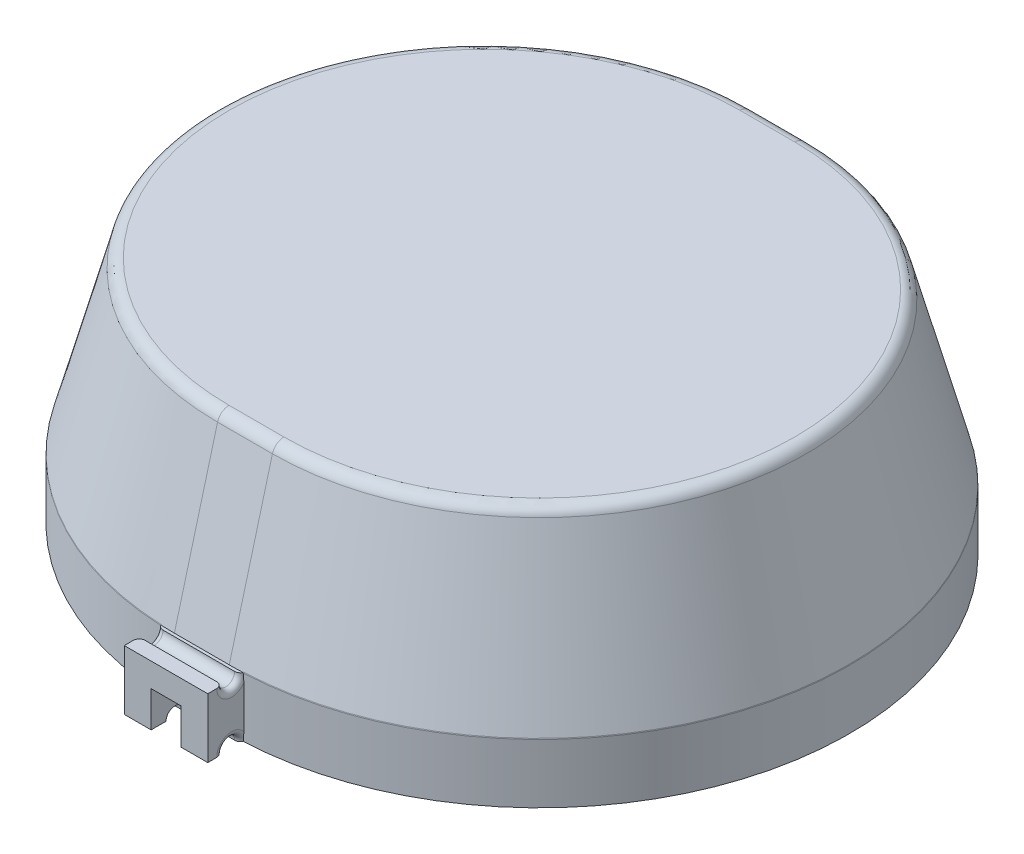
SolidWorks part; units mm, degrees
material "ABS"
ref_plane "Front Plane" through (0, 0, 0) normal (0, 0, 1) x (1, 0, 0)
ref_plane "Top Plane" through (0, 0, 0) normal (0, 1, 0) x (1, 0, 0)
ref_plane "Right Plane" through (0, 0, 0) normal (1, 0, 0) x (0, 0, -1)
ref_axis "Center" through (0, 21.7875, 0) along (0, -1, 0)
sketch "Sketch1" plane through (0, 0, 0) normal (0, 1, 0) x (1, 0, 0)
  line L0 (-2.3, 0) -> (2.3, 0) construction
  line L1 (-2.3, 25) -> (2.3, 25)
  line L2 (-2.3, -25) -> (2.3, -25)
  line L3 (-2.3, 0) -> (2.3, 0) construction
  line L4 (-2.3, 26) -> (2.3, 26)
  line L5 (-2.3, -26) -> (2.3, -26)
  arc A0 (-2.3, 25) -> (-2.3, -25) centre (-2.3, 0) ccw
  arc A1 (2.3, -25) -> (2.3, 25) centre (2.3, 0) ccw
  arc A2 (-2.3, 26) -> (-2.3, -26) centre (-2.3, 0) ccw
  arc A3 (2.3, -26) -> (2.3, 26) centre (2.3, 0) ccw
  point P2 (0, 0)
  point P9 (0, 0)
  dimension "D1" = 4.6
  dimension "D2" = 25
  dimension "D3" = 26
extrude "Boss-Extrude2" add sketch "Sketch1" along normal blind 5
sketch "Sketch2" plane through (0, 0, 0) normal (0, 1, 0) x (1, 0, 0)
  line L0 (-3.5, -25.9723) -> (-3.5, -27) construction
  line L1 (3.5, -25.9723) -> (3.5, -27) construction
  line L2 (-4.25, -25) -> (-4.25, -27)
  line L3 (4.25, -25) -> (4.25, -27)
  line L4 (-2.3, -25) -> (2.3, -25) construction
  line L5 (-4.25, -25) -> (4.25, -25)
  line L6 (0, -27) -> (0, -26) construction
  line L7 (-2.3, -26) -> (2.3, -26) construction
  line L8 (0, -27) -> (-3.5, -27) construction
  line L9 (0, -27) -> (3.5, -27) construction
  arc A0 (-3.5, -27) -> (3.5, -27) centre (0, -27) ccw construction
  arc A1 (-2.3, 26) -> (-2.3, -26) centre (-2.3, 0) ccw construction
  arc A3 (4.25, -27) -> (-4.25, -27) centre (0, -27) cw
  arc A4 (2.3, -26) -> (2.3, 26) centre (2.3, 0) ccw construction
  dimension "D1" = 2
  dimension "D2" = 0.75
  dimension "D3" = 0.75
  dimension "D4" = 3.5
ref_axis "F1" through (-2.3, 0, 0) along (0, 1, 0)
ref_axis "F2" through (2.3, 0, 0) along (0, 1, 0)
sketch "Sketch8" plane through (0, 0, 0) normal (1, 0, 0) x (0, 0, -1)
  line L1 (-25, 5) -> (-23.69, 5)
  line L2 (-25, 5) -> (-25, 3)
  line L3 (-25, 3) -> (-23.69, 3)
  line L4 (-23.69, 5) -> (-23.69, 3)
  dimension "D1" = 1.31
sweep "Sweep1" add profiles "Sketch8" path "Sketch1<2>"
sketch "Sketch1<2>" plane through (0, 0, 0) normal (0, 1, 0) x (1, 0, 0) same geometry as "Sketch1"
sketch "Sketch5" plane through (0, 0, 0) normal (-1, 0, 0) x (0, 0, 1)
  line L0 (-26, 5) -> (-22.1817, 19.25)
  line L1 (-22.1817, 19.25) -> (0, 19.25)
  line L2 (0, 19.25) -> (0, 18)
  line L3 (0, 18) -> (-21.2226, 18)
  line L4 (-21.2226, 18) -> (-24.7059, 5)
  line L7 (-24.7059, 5) -> (-26, 5)
  line L11 (-26, 5) -> (-26, 21.0394) construction
  line L12 (0, 21.7875) -> (0, -1.0375) construction
  dimension "D1" = 1.25
  dimension "D2" = 15
  dimension "D3" = 1.25
  dimension "D4" = 18
extrude "Boss-Extrude4" add sketch "Sketch5" along normal blind 2.3 and the other way blind 2.3
sketch "Sketch7" plane through (-2.3, 0, 0) normal (-1, 0, 0) x (0, 0, 1)
  line L0 (-26, 5) -> (-22.1817, 19.25)
  line L1 (-22.1817, 19.25) -> (0, 19.25)
  line L2 (0, 19.25) -> (0, 18)
  line L3 (0, 18) -> (-21.2226, 18)
  line L4 (-21.2226, 18) -> (-24.7059, 5)
  line L5 (-24.7059, 5) -> (-26, 5)
revolve "Revolve2" add sketch "Sketch7" angle 180 about axis through (-2.3, 0, 0) along (0, 1, 0)
mirror "Mirror1" about plane through (0, 0, 0) normal (0, 0, 1) of "Boss-Extrude4"
mirror "Mirror2" about plane through (0, 0, 0) normal (1, 0, 0) of "Revolve2"
sketch "Sketch11" plane through (0, 0, -25) normal (0, 0, -1) x (-1, 0, 0)
  line L0 (2.3, 5) -> (2.3, 0) construction
  line L1 (-2.3, 3) -> (2.3, 3)
  line L2 (-2.3, 3) -> (-2.3, 1.5)
  line L3 (-2.3, 1.5) -> (2.3, 1.5)
  line L4 (2.3, 3) -> (2.3, 1.5)
  line L5 (2.3, 3) -> (-2.3, 3) construction
  dimension "D1" = 1.5
extrude "Cut-Extrude5" cut sketch "Sketch11" along normal up to next (1 mm away) draft 5
fillet "Fillet8" radius 0.25 3 edges at (2.3, 2.25, -25) (0, 1.5, -25) (-2.3, 2.25, -25)
sketch "Sketch12" plane through (0, 3, 0) normal (0, -1, 0) x (1, 0, 0)
  line L0 (-3.5, 25) -> (-3.5, 29)
  line L1 (-3.5, 29) -> (3.5, 29)
  line L2 (3.5, 29) -> (3.5, 25)
  line L3 (3.5, 25) -> (-3.5, 25)
  line L4 (0, 25) -> (0, 23.69) construction
  line L5 (2.3, 25) -> (0, 25) construction
  point P2 (0, 25)
  dimension "D1" = 7
  dimension "D2" = 4
extrude "Boss-Extrude6" add sketch "Sketch12" along normal up to surface (3 mm away) and the other way up to vertex (2 mm away) up to face at (0, 0, 0) other way up to point (-2.3, 5, 26)
sketch "Sketch13" plane through (0, 0, 0) normal (0, -1, 0) x (1, 0, 0)
  line L0 (-2.3, 25) -> (2.3, 25) construction
  line L1 (1.25, 25) -> (-1.25, 25)
  line L2 (1.25, 25) -> (1.25, 29)
  line L3 (1.25, 29) -> (-1.25, 29)
  line L4 (-1.25, 25) -> (-1.25, 29)
  line L8 (0, 29) -> (0, 25) construction
  point P6 (0, 25)
  dimension "D1" = 2.5
  dimension "D2" = 4
extrude "Cut-Extrude6" cut sketch "Sketch13" against normal up to surface (3 mm away) up to face at (1.725, 3, 24.5087)
sketch "Sketch14" plane through (-3.5, 0, 0) normal (-1, 0, 0) x (0, 0, 1)
  line L0 (25.9723, 0) -> (29, 0) construction
  line L1 (29, 5) -> (25.9723, 5) construction
  line L2 (27.75, 5) -> (26.25, 5)
  line L3 (27.75, 0) -> (26.25, 0)
  line L4 (29, 0) -> (29, 5) construction
  arc A0 (26.25, 0) -> (27.75, 0) centre (27, 0) cw
  arc A1 (26.25, 5) -> (27.75, 5) centre (27, 5) ccw
  dimension "D1" = 0.75
  dimension "D2" = 0.75
  dimension "D3" = 2
extrude "Cut-Extrude7" cut sketch "Sketch14" against normal up to surface (7 mm away) up to face at (3.5, 2.5, 27.4861)
fillet "Fillet9" radius 0.5 4 edges at (3.5, 0.75, 27) (-3.5, 0.75, 27) (-3.5, 4.25, 27) (3.5, 4.25, 27)
fillet "Fillet10" radius 0.25 2 edges at (1.25, 1.5, 25) (-1.25, 1.5, 25)
fillet "Fillet6" radius 0.3 3 edges at (28.2937, 5, -0.5735) (0, 5, -26) (-28.2937, 5, -0.5735)
fillet "Fillet7" radius 1 8 edges at (0, 18, 21.2226) (23.5226, 18, 0) (0, 18, -21.2226) (0, 19.25, 22.1817) (24.4817, 19.25, 0) (0, 19.25, -22.1817) (-23.5226, 18, 0) (-24.4817, 19.25, 0)
